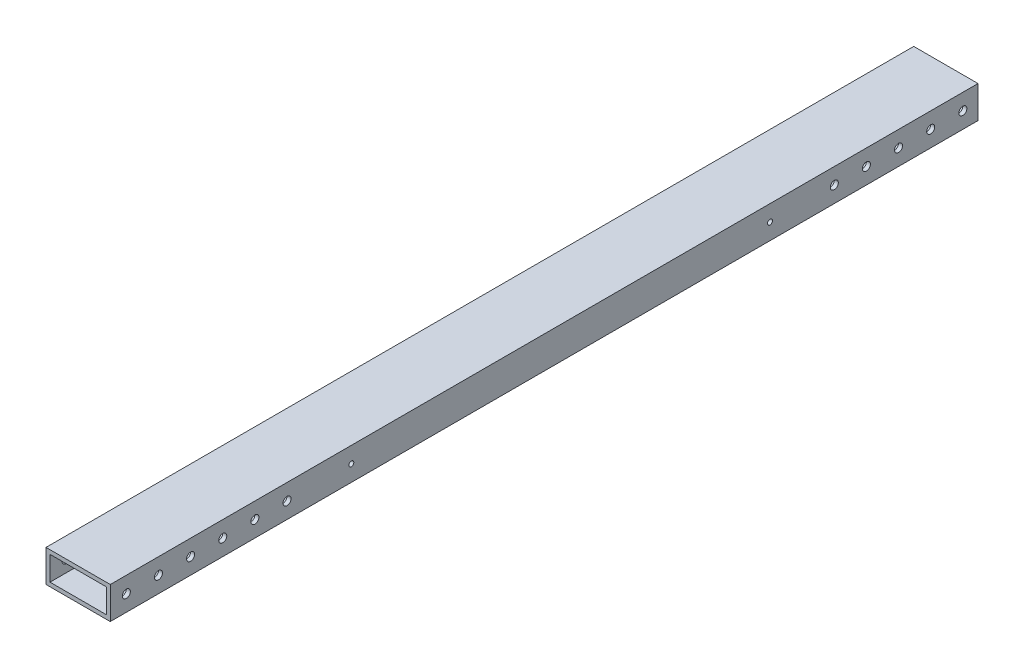
SolidWorks part; units mm, degrees
material "6061 Alloy"
ref_plane "Front Plane" through (0, 0, 0) normal (0, 0, 1) x (1, 0, 0)
ref_plane "Top Plane" through (0, 0, 0) normal (0, 1, 0) x (1, 0, 0)
ref_plane "Right Plane" through (0, 0, 0) normal (1, 0, 0) x (0, 0, -1)
sketch "Sketch1" plane through (0, 0, 0) normal (0, 0, 1) x (1, 0, 0)
  line L0 (-22.225, 9.525) -> (22.225, 9.525)
  line L2 (-25.4, 12.7) -> (25.4, 12.7)
  line L3 (-25.4, 12.7) -> (-25.4, -12.7)
  line L4 (-25.4, -12.7) -> (25.4, -12.7)
  line L5 (25.4, 12.7) -> (25.4, -12.7)
  line L10 (22.225, 9.525) -> (22.225, -9.525)
  line L11 (-22.225, -9.525) -> (22.225, -9.525)
  line L12 (-22.225, 9.525) -> (-22.225, -9.525)
  point P12 (0, 12.7)
  point P14 (25.4, 0)
  dimension "Wall Thickness" = 3.175
  dimension "Outside Width" = 50.8
  dimension "Outside Height" = 25.4
  dimension "Inside Height" = 19.05
  dimension "Inside Width" = 44.45
sketch "Sketch2" plane through (0, 0, 0) normal (1, 0, 0) x (0, 0, -1)
  line L0 (342.9, 0) -> (-342.9, 0)
  point P4 (0, 0)
  point P7 (-342.9, 0)
  point P10 (342.9, 0)
  dimension "Length" = 685.8
sketch "Sketch3" plane through (0, 0, 0) normal (0, 0, 1) x (1, 0, 0)
  line L21 (25.4, 12.7) -> (-25.4, 12.7)
  line L22 (25.4, -12.7) -> (25.4, 12.7)
  line L23 (-25.4, -12.7) -> (25.4, -12.7)
  line L24 (-25.4, 12.7) -> (-25.4, -12.7)
  line L25 (25.4, 12.7) -> (-25.4, 12.7)
  line L26 (25.4, -12.7) -> (25.4, 12.7)
  line L27 (-25.4, -12.7) -> (25.4, -12.7)
  line L28 (-25.4, 12.7) -> (-25.4, -12.7)
  line L29 (22.225, 9.525) -> (-22.225, 9.525)
  line L30 (22.225, -9.525) -> (22.225, 9.525)
  line L31 (-22.225, -9.525) -> (22.225, -9.525)
  line L32 (-22.225, 9.525) -> (-22.225, -9.525)
  line L33 (22.225, 9.525) -> (-22.225, 9.525)
  line L34 (22.225, -9.525) -> (22.225, 9.525)
  line L35 (-22.225, -9.525) -> (22.225, -9.525)
  line L36 (-22.225, 9.525) -> (-22.225, -9.525)
  dimension "D1" = 0
  dimension "D2" = 0
extrude "Boss-Extrude1" add sketch "Sketch3" along normal up to vertex (342.9 mm away) and the other way up to vertex (342.9 mm away) up to point (0, 0, 342.9) other way up to point (0, 0, -342.9)
sketch "Drawing Reference" plane through (0, 0, 0) normal (1, 0, 0) x (0, 0, -1)
  line L0 (-342.9, 0) -> (342.9, 0) construction
  line L1 (0, -12.7) -> (0, 12.7) construction
  line L2 (-342.9, -12.7) -> (342.9, -12.7) construction
  line L5 (-342.9, 12.7) -> (342.9, 12.7) construction
  point P7 (-306.324, 0)
  point P8 (306.324, 0)
  dimension "D1" = 36.576
sketch "Sketch5" plane through (25.4, 0, 0) normal (1, 0, 0) x (0, 0, -1)
  line L0 (-342.9, 0) -> (-279.4, 0)
  line L1 (-342.9, -12.7) -> (-342.9, 12.7) construction
  line L2 (-279.4, 0) -> (-254, 0)
  line L3 (-254, 0) -> (-228.6, 0)
  line L4 (-228.6, 0) -> (-203.2, 0)
sketch "Sketch8" plane through (25.4, 0, 0) normal (1, 0, 0) x (0, 0, -1)
  line L0 (342.9, 0) -> (305.5118, 0)
  line L1 (342.9, -12.7) -> (342.9, 12.7) construction
  line L2 (305.5118, 0) -> (280.1118, 0)
  line L3 (280.1118, 0) -> (254.7118, 0)
  line L4 (254.7118, 0) -> (229.3118, 0)
hole_wizard "1/4 (0.25) Diameter Hole3" positions "Sketch12" profile "Sketch13" hole size "1/4" standard "ANSI Inch" end condition through all
sketch "Sketch12" plane through (-25.4, 0, 0) normal (-1, 0, 0) x (0, 0, 1)
  point P0 (-330.9118, 0)
sketch "Sketch13" plane through (-25.4, 0, -330.9118) normal (0, 1, 0) x (0, 0, 1)
  line L0 (0, 0) -> (0, 50.8)
  line L1 (0, 50.8) -> (3.175, 50.8)
  line L2 (3.175, 50.8) -> (3.175, 0)
  line L5 (3.175, 0) -> (0, 0)
  line L11 (0, -6.35) -> (0, 107.95) construction
  dimension "Thru Hole Dia." = 6.35
  dimension "Thru Hole Depth" = 50.8
hole_wizard "1/4 (0.25) Diameter Hole4" positions "Sketch14" profile "Sketch15" hole size "1/4" standard "ANSI Inch" end condition through all
sketch "Sketch14" plane through (-25.4, 0, 0) normal (-1, 0, 0) x (0, 0, 1)
  point P0 (304.8, 0)
  point P3 (330.2, 0)
sketch "Sketch15" plane through (-25.4, 0, 304.8) normal (0, 1, 0) x (0, 0, 1)
  line L0 (0, 0) -> (0, 50.8)
  line L1 (0, 50.8) -> (3.175, 50.8)
  line L2 (3.175, 50.8) -> (3.175, 0)
  line L5 (3.175, 0) -> (0, 0)
  line L11 (0, -6.35) -> (0, 107.95) construction
  dimension "Thru Hole Dia." = 6.35
  dimension "Thru Hole Depth" = 50.8
hole_wizard "1/4 (0.25) Diameter Hole5" positions "Sketch17" profile "Sketch18" hole size "1/4" standard "ANSI Inch" end condition through all
sketch "Sketch17" plane through (25.4, 0, 0) normal (1, 0, 0) x (0, 0, -1)
  point P0 (305.5118, 0)
  point P3 (280.1118, 0)
sketch "Sketch18" plane through (25.4, 0, -305.5118) normal (0, 1, 0) x (0, 0, -1)
  line L0 (0, 0) -> (0, 50.8)
  line L1 (0, 50.8) -> (3.175, 50.8)
  line L2 (3.175, 50.8) -> (3.175, 0)
  line L5 (3.175, 0) -> (0, 0)
  line L11 (0, -6.35) -> (0, 107.95) construction
  dimension "Thru Hole Dia." = 6.35
  dimension "Thru Hole Depth" = 50.8
hole_wizard "1/4 (0.25) Diameter Hole6" positions "Sketch19" profile "Sketch20" hole size "1/4" standard "ANSI Inch" end condition through all
sketch "Sketch19" plane through (25.4, 0, 0) normal (1, 0, 0) x (0, 0, -1)
  point P0 (229.3118, 0)
  point P3 (254.7118, 0)
sketch "Sketch20" plane through (25.4, 0, -229.3118) normal (0, 1, 0) x (0, 0, -1)
  line L0 (0, 0) -> (0, 50.8)
  line L1 (0, 50.8) -> (3.175, 50.8)
  line L2 (3.175, 50.8) -> (3.175, 0)
  line L5 (3.175, 0) -> (0, 0)
  line L11 (0, -6.35) -> (0, 107.95) construction
  dimension "Thru Hole Dia." = 6.35
  dimension "Thru Hole Depth" = 50.8
hole_wizard "1/4 (0.25) Diameter Hole7" positions "Sketch21" profile "Sketch22" hole size "1/4" standard "ANSI Inch" end condition through all
sketch "Sketch21" plane through (25.4, 0, 0) normal (1, 0, 0) x (0, 0, -1)
  point P0 (-203.2, 0)
  point P3 (-228.6, 0)
sketch "Sketch22" plane through (25.4, 0, 203.2) normal (0, 1, 0) x (0, 0, -1)
  line L0 (0, 0) -> (0, 50.8)
  line L1 (0, 50.8) -> (3.175, 50.8)
  line L2 (3.175, 50.8) -> (3.175, 0)
  line L5 (3.175, 0) -> (0, 0)
  line L11 (0, -6.35) -> (0, 107.95) construction
  dimension "Thru Hole Dia." = 6.35
  dimension "Thru Hole Depth" = 50.8
hole_wizard "1/4 (0.25) Diameter Hole8" positions "Sketch23" profile "Sketch24" hole size "1/4" standard "ANSI Inch" end condition through all
sketch "Sketch23" plane through (25.4, 0, 0) normal (1, 0, 0) x (0, 0, -1)
  point P0 (-279.4, 0)
  point P3 (-254, 0)
sketch "Sketch24" plane through (25.4, 0, 279.4) normal (0, 1, 0) x (0, 0, -1)
  line L0 (0, 0) -> (0, 50.8)
  line L1 (0, 50.8) -> (3.175, 50.8)
  line L2 (3.175, 50.8) -> (3.175, 0)
  line L5 (3.175, 0) -> (0, 0)
  line L11 (0, -6.35) -> (0, 107.95) construction
  dimension "Thru Hole Dia." = 6.35
  dimension "Thru Hole Depth" = 50.8
sketch "Sketch25" plane through (25.4, 0, 0) normal (1, 0, 0) x (0, 0, -1)
  line L0 (-203.2, 0) -> (-152.4, 0)
  line L1 (229.3118, 0) -> (178.5118, 0)
hole_wizard "5/32 (0.15625) Diameter Hole1" positions "Sketch26" profile "Sketch27" hole size "5/32" standard "ANSI Inch" end condition through all
sketch "Sketch26" plane through (25.4, 0, 0) normal (1, 0, 0) x (0, 0, -1)
  point P0 (-152.4, 0)
  point P3 (178.5118, 0)
sketch "Sketch27" plane through (25.4, 0, 152.4) normal (0, 1, 0) x (0, 0, -1)
  line L0 (0, 0) -> (0, 50.8)
  line L1 (0, 50.8) -> (1.9844, 50.8)
  line L2 (1.9844, 50.8) -> (1.9844, 0)
  line L5 (1.9844, 0) -> (0, 0)
  line L11 (0, -6.35) -> (0, 107.95) construction
  dimension "Thru Hole Dia." = 3.9688
  dimension "Thru Hole Depth" = 50.8
sketch "Sketch30" plane through (-25.4, 0, 0) normal (-1, 0, 0) x (0, 0, 1)
  line L0 (203.2, 0) -> (184.15, 0)
  line L1 (203.2, 0) -> (152.4, 0) construction
  point P0 (-210.2618, 0)
hole_wizard "1/2 (0.5) Diameter Hole1" positions "Sketch33" profile "Sketch34" hole size "1/2" standard "ANSI Inch"
sketch "Sketch33" plane through (-25.4, 0, 0) normal (-1, 0, 0) x (0, 0, 1)
  point P0 (-210.2618, 0)
  point P3 (184.15, 0)
sketch "Sketch34" plane through (-25.4, 0, -210.2618) normal (0, 1, 0) x (0, 0, 1)
  line L0 (0, 0) -> (0, 10.1655)
  line L1 (0, 10.1655) -> (6.35, 6.35)
  line L2 (6.35, 6.35) -> (6.35, 0)
  line L5 (6.35, 0) -> (0, 0)
  line L10 (0, 10.1655) -> (-6.35, 6.35) construction
  line L11 (0, -6.35) -> (0, 107.95) construction
  dimension "Hole Dia." = 12.7
  dimension "Hole Depth" = 6.35
  dimension "Drill Angle" = 118
equation "\"D1@Drawing Reference\"=\"Outside Width@Sketch1\" * 0.72"
